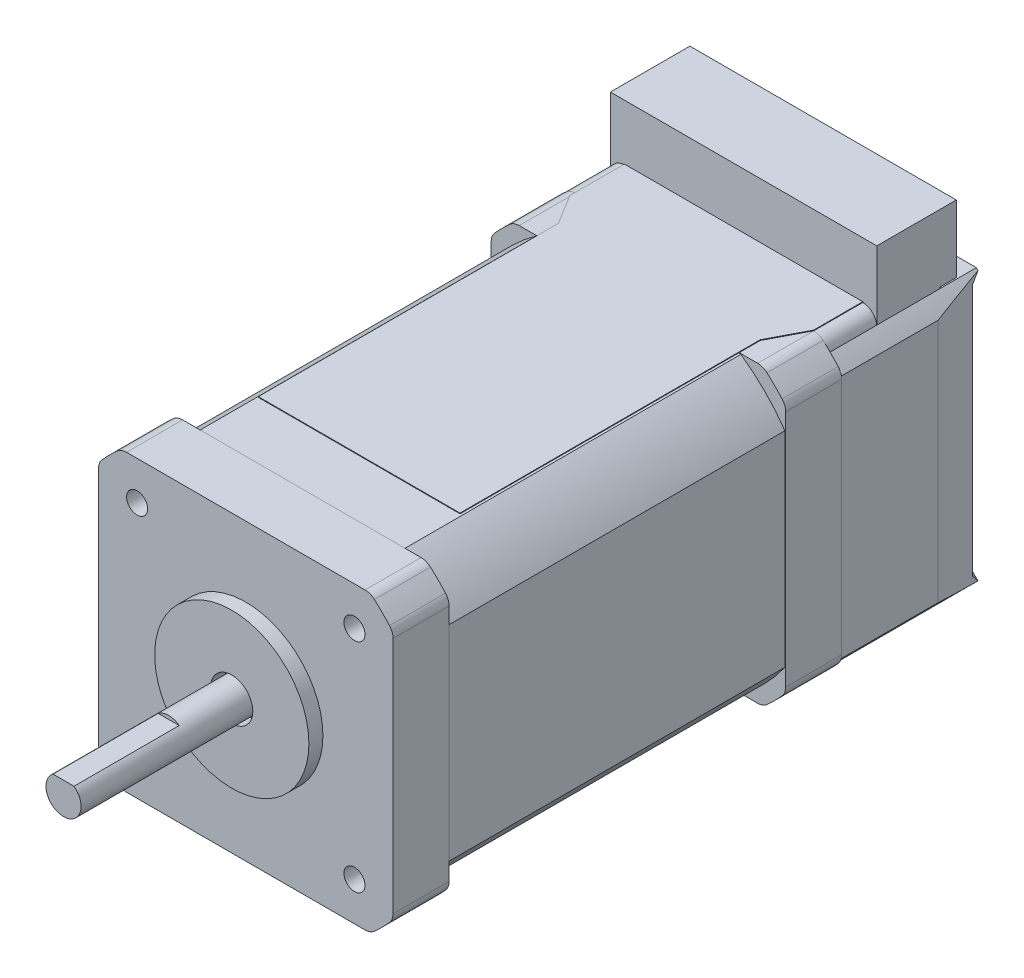
SolidWorks part; units mm, degrees
ref_plane "Ebene vorne" through (0, 0, 0) normal (0, 0, 1) x (1, 0, 0)
ref_plane "Ebene oben" through (0, 0, 0) normal (0, 1, 0) x (1, 0, 0)
ref_plane "Ebene rechts" through (0, 0, 0) normal (1, 0, 0) x (0, 0, -1)
sketch "Skizze1" plane through (0, 0, 0) normal (0, 0, 1) x (1, 0, 0)
  line L1 (-21, -21) -> (21, -21)
  line L2 (-21, -21) -> (-21, 21)
  line L3 (-21, 21) -> (21, 21)
  line L4 (21, -21) -> (21, 21)
  line L5 (-21, -21) -> (21, 21) construction
  line L6 (-21, 21) -> (21, -21) construction
  point P0 (0, 0)
  dimension "D1" = 42
  dimension "D2" = 42
extrude "Aufsatz-Linear austragen1" add sketch "Skizze1" along normal mid plane 64
sketch "Skizze2" plane through (0, 0, 32) normal (0, 0, 1) x (1, 0, 0)
  circle A0 centre (0, 0) radius 27.5
  dimension "D1" = 55
sketch "Skizze3" plane through (0, 0, 32) normal (0, 0, 1) x (1, 0, 0)
  circle A0 centre (0, 0) radius 11
  circle A1 centre (0, 0) radius 3
  dimension "D1" = 22
  dimension "D2" = 6
extrude "Aufsatz-Linear austragen2" add sketch "Skizze3" along normal blind 2
sketch "Skizze4" plane through (0, 0, 32) normal (0, 0, 1) x (1, 0, 0)
  line L1 (-15.5, -15.5) -> (15.5, -15.5)
  line L2 (-15.5, -15.5) -> (-15.5, 15.5)
  line L3 (-15.5, 15.5) -> (15.5, 15.5)
  line L4 (15.5, -15.5) -> (15.5, 15.5)
  line L5 (-15.5, -15.5) -> (15.5, 15.5) construction
  line L6 (-15.5, 15.5) -> (15.5, -15.5) construction
  point P0 (0, 0)
  dimension "D1" = 31
  dimension "D2" = 31
sketch "Skizze5" plane through (0, 0, 32) normal (0, 0, 1) x (1, 0, 0)
  circle A0 centre (-15.5, 15.5) radius 1.5
  circle A1 centre (15.5, 15.5) radius 1.5
  circle A2 centre (-15.5, -15.5) radius 1.5
  circle A3 centre (15.5, -15.5) radius 1.5
  dimension "D1" = 3
extrude "Schnitt-Linear austragen2" cut sketch "Skizze5" against normal blind 10
sketch "Skizze6" plane through (0, 0, 34) normal (0, 0, 1) x (1, 0, 0)
  circle A0 centre (0, 0) radius 2.5
  dimension "D1" = 5
extrude "Aufsatz-Linear austragen3" add sketch "Skizze6" along normal blind 24 and the other way blind 10
sketch "Skizze10" plane through (0, 0, 58) normal (0, 0, 1) x (1, 0, 0)
  line L1 (-6.775, 11.5682) -> (7.5774, 11.5682)
  line L2 (-6.775, 11.5682) -> (-6.775, 2)
  line L3 (-6.775, 2) -> (7.5774, 2)
  line L4 (7.5774, 11.5682) -> (7.5774, 2)
  dimension "D1" = 2
extrude "Schnitt-Linear austragen4" cut sketch "Skizze10" against normal blind 15
ref_plane "Ebene1" through (0, 0, 0) normal (1, 0, 0) x (0, 0, -1)
ref_plane "Ebene2" through (0, 0, 0) normal (0, 1, 0) x (1, 0, 0)
extrude "Schnitt-Linear austragen5" cut sketch "Skizze2" against normal through all flip side to cut
sketch "Skizze11" plane through (0, 0, 32) normal (0, 0, 1) x (1, 0, 0)
  line L0 (-14.6096, 20.9) -> (14.6096, 20.9)
  line L1 (-20.9, 14.6096) -> (-20.9, -14.6096)
  line L2 (-14.6096, -20.9) -> (14.6096, -20.9)
  line L3 (20.9, -14.6096) -> (20.9, 14.6096)
  line L4 (21, -17.7553) -> (21, 17.7553) construction
  line L5 (17.7553, 21) -> (-17.7553, 21) construction
  line L6 (-21, 17.7553) -> (-21, -17.7553) construction
  line L7 (-17.7553, -21) -> (17.7553, -21) construction
  arc A0 (-20.9, -14.6096) -> (-14.6096, -20.9) centre (0, 0) ccw
  circle A1 centre (0, 0) radius 28.2253
  arc A2 (14.6096, -20.9) -> (20.9, -14.6096) centre (0, 0) ccw
  arc A3 (20.9, 14.6096) -> (14.6096, 20.9) centre (0, 0) ccw
  arc A4 (-14.6096, 20.9) -> (-20.9, 14.6096) centre (0, 0) ccw
  dimension "D1" = 51
  dimension "D2" = 0.1
  dimension "D3" = 0.1
  dimension "D4" = 0.1
  dimension "D5" = 0.1
extrude "Schnitt-Linear austragen6" cut sketch "Skizze11" against normal offset from surface (48 mm away) 8 from offset 8 up to face at (0, 0, -32) offset against normal yes
fillet "Verrundung1" radius 2 16 edges at (17.7553, -21, 28) (21, -17.7553, 28) (21, -17.7553, -28) (17.7553, -21, -28) (-21, -17.7553, -28) (-17.7553, -21, -28) (-17.7553, -21, 28) (-21, -17.7553, 28) (-17.7553, 21, 28) (-21, 17.7553, 28) (-21, 17.7553, -28) (-17.7553, 21, -28) (21, 17.7553, -28) (17.7553, 21, -28) (21, 17.7553, 28) (17.7553, 21, 28)
sketch "Skizze12" plane through (0, 0, -32) normal (0, 0, -1) x (-1, 0, 0)
  line L0 (-17.0074, 21) -> (17.0074, 21) construction
  line L1 (-19, 21) -> (19, 21)
  line L2 (-19, 21) -> (-19, 6)
  line L3 (-19, 6) -> (19, 6)
  line L4 (19, 21) -> (19, 6)
  dimension "D1" = 19
  dimension "D2" = 19
  dimension "D3" = 15
extrude "Aufsatz-Linear austragen4" add sketch "Skizze12" along normal blind 8 separate body
fillet "Verrundung2" radius 2 2 edges at (-19, 21, -36) (19, 21, -36)
sketch "Skizze13" plane through (0, 0, -40) normal (0, 0, -1) x (-1, 0, 0)
  line L1 (-19, 6) -> (19, 6)
  line L2 (-19, 6) -> (-19, 19)
  line L3 (-19, 19) -> (19, 19)
  line L4 (19, 6) -> (19, 19)
  arc A0 (19, 19) -> (17, 21) centre (17, 19) ccw construction
extrude "Aufsatz-Linear austragen5" add sketch "Skizze13" along normal blind 8 separate body
sketch "Skizze15" plane through (0, 19, 0) normal (0, 1, 0) x (1, 0, 0)
  line L0 (-19, 40) -> (19, 40) construction
  line L1 (0.5, 40.6) -> (3, 40.6)
  line L2 (0.5, 40.6) -> (0.5, 47.4)
  line L3 (0.5, 47.4) -> (3, 47.4)
  line L4 (3, 40.6) -> (3, 47.4)
  line L5 (-19, 48) -> (19, 48) construction
  dimension "D1" = 2.5
  dimension "D2" = 0.5
  dimension "D3" = 0.6
  dimension "D4" = 0.6
extrude "Schnitt-Linear austragen7" cut sketch "Skizze15" against normal blind 8
pattern_linear "Lineares Muster1" count 5 spacing 3.5 along (1, 0, 0) of "Schnitt-Linear austragen7"
mirror "Spiegeln1" about plane through (0, 0, 0) normal (1, 0, 0) of "Lineares Muster1", "Schnitt-Linear austragen7"
sketch "Skizze16" plane through (0, 0, -32) normal (0, 0, -1) x (-1, 0, 0)
  line L0 (-19.2, 19.4075) -> (-19.2, 5.7074)
  line L1 (-19.2, 5.7074) -> (19.2, 5.7074)
  line L2 (19.2, 5.7074) -> (19.2, 19.4075)
  line L3 (-21, 17.4439) -> (-21, -17.4439)
  line L4 (-17.4439, -21) -> (17.4439, -21)
  line L5 (21, -17.4439) -> (21, 17.4439)
  arc A0 (-19.2, 19.4075) -> (-21, 17.4439) centre (0, 0) ccw
  arc A1 (21, 17.4439) -> (19.2, 19.4075) centre (0, 0) ccw
  arc A2 (-21, -17.4439) -> (-17.4439, -21) centre (0, 0) ccw
  arc A3 (17.4439, -21) -> (21, -17.4439) centre (0, 0) ccw
  dimension "D1" = 19.2
  dimension "D3" = 54.6
  dimension "D2" = 19.2
  dimension "D4" = 21
  dimension "D5" = 21
  dimension "D6" = 21
extrude "Aufsatz-Linear austragen6" add sketch "Skizze16" along normal blind 16 separate body
sketch "Skizze17" plane through (0, 0, -48) normal (0, 0, -1) x (-1, 0, 0)
  line L0 (-19.2, 19.4075) -> (19.2, 19.4075)
  line L1 (21, 17.4439) -> (21, -17.4439)
  line L2 (-21, -17.4439) -> (-21, 17.4439)
  line L3 (-17.4439, -21) -> (17.4439, -21)
  arc A0 (17.4439, -21) -> (21, -17.4439) centre (0, 0) ccw
  arc A1 (21, 17.4439) -> (19.2, 19.4075) centre (0, 0) ccw
  arc A2 (-21, -17.4439) -> (-17.4439, -21) centre (0, 0) ccw
  arc A3 (-19.2, 19.4075) -> (-21, 17.4439) centre (0, 0) ccw
extrude "Aufsatz-Linear austragen7" add sketch "Skizze17" along normal blind 5
sketch "Skizze18" plane through (0, 0, -53) normal (0, 0, -1) x (-1, 0, 0)
  line L0 (0, 2.3344) -> (0, -9.554) construction
  line L1 (0, 22.3327) -> (0, -22.3327) construction
  line L2 (5.2211, 2.3344) -> (5.2211, -9.554)
  line L3 (-5.2211, 2.3344) -> (-5.2211, -9.554)
  line L4 (-9.6893, 19.4075) -> (-2.5, 12.2182)
  line L5 (19.2, 19.4075) -> (-19.2, 19.4075) construction
  line L6 (-2.5, 12.2182) -> (-2.5, 6.9181)
  line L7 (-2.5, -14.9333) -> (-8.5667, -21)
  line L8 (-17.4439, -21) -> (17.4439, -21) construction
  line L9 (2.5, 12.2182) -> (9.6893, 19.4075)
  line L10 (9.6893, 19.4075) -> (-9.6893, 19.4075)
  line L11 (2.5, 12.2182) -> (2.5, 6.9181)
  line L12 (2.5, -14.9333) -> (8.5667, -21)
  line L13 (8.5667, -21) -> (-8.5667, -21)
  line L14 (-2.5, -14.1377) -> (-2.5, -14.9333)
  line L15 (2.5, -14.1377) -> (2.5, -14.9333)
  arc A0 (5.2211, 2.3344) -> (2.5, 6.9181) centre (0, 2.3344) ccw
  arc A1 (-5.2211, -9.554) -> (-2.5, -14.1377) centre (0, -9.554) ccw
  arc A2 (-2.5, 6.9181) -> (-5.2211, 2.3344) centre (0, 2.3344) ccw
  arc A3 (2.5, -14.1377) -> (5.2211, -9.554) centre (0, -9.554) ccw
  point P5 (0, -3.6098)
  dimension "D1" = 2.5
  dimension "D2" = 2.5
  dimension "D3" = 45
  dimension "D4" = 45
extrude "Schnitt-Linear austragen8" cut sketch "Skizze18" against normal blind 1
sketch "Skizze19" plane through (0, 0, -52) normal (0, 0, -1) x (-1, 0, 0)
  line L0 (0, 7.979) -> (0, 11.017) construction
  line L1 (0, 22.3327) -> (0, -22.3327) construction
  line L2 (-0.7738, 7.979) -> (-0.7738, 11.017)
  line L3 (0.7738, 7.979) -> (0.7738, 11.017)
  arc A0 (-0.7738, 7.979) -> (0.7738, 7.979) centre (0, 7.979) ccw
  arc A1 (0.7738, 11.017) -> (-0.7738, 11.017) centre (0, 11.017) ccw
  point P5 (0, 9.498)
extrude "Aufsatz-Linear austragen8" add sketch "Skizze19" along normal blind 1
sketch "Skizze20" plane through (0, 0, -53) normal (0, 0, -1) x (-1, 0, 0)
  line L1 (-11.6444, 10.6744) -> (-11.6444, -9.9681)
  line L4 (-24.1419, -18.4477) -> (-24.1419, 18.4477)
  line L6 (-20.124, 18.4477) -> (-11.6444, 10.6744)
  line L7 (-20.124, 18.4477) -> (-24.1419, 18.4477)
  line L8 (-20.124, 18.4477) -> (-20.124, -18.4477) construction
  line L9 (-20.124, -18.4477) -> (-11.6444, -9.9681)
  line L10 (-20.124, -18.4477) -> (-24.1419, -18.4477)
  arc A0 (-21, -17.4439) -> (-17.4439, -21) centre (0, 0) ccw construction
  arc A1 (-19.2, 19.4075) -> (-21, 17.4439) centre (0, 0) ccw construction
extrude "Schnitt-Linear austragen9" cut sketch "Skizze20" against normal blind 1
mirror "Spiegeln2" about plane through (0, 0, 0) normal (1, 0, 0) of "Schnitt-Linear austragen9"
chamfer "Fase1" distance 1 angle 45 18 edges at (-15.8842, 14.561, -53) (-11.6444, 0.3532, -53) (-15.8842, -14.2079, -53) (6.0947, 15.8128, -53) (2.5, 9.5681, -53) (4.4896, 4.9996, -53) (5.2211, -3.6098, -53) (4.4896, -12.2192, -53) (5.5334, -17.9666, -53) (-5.5334, -17.9666, -53) (-4.4896, -12.2192, -53) (-5.2211, -3.6098, -53) (-4.4896, 4.9996, -53) (-2.5, 9.5681, -53) (-6.0947, 15.8128, -53) (15.8842, -14.2079, -53) (11.6444, 0.3532, -53) (15.8842, 14.561, -53)
sketch "Skizze21" plane through (0, 19.4075, 0) normal (0, 1, 0) x (1, 0, 0)
  line L0 (19.4347, 53) -> (21.4638, 43.6127)
  line L1 (21.4638, 43.6127) -> (21.4638, 53)
  line L2 (21.4638, 53) -> (19.4347, 53)
  line L3 (-19.4347, 53) -> (-21.351, 43.7732)
  line L4 (-21.351, 43.7732) -> (-21.351, 53)
  line L5 (-21.351, 53) -> (-19.4347, 53)
extrude "Schnitt-Linear austragen10" cut sketch "Skizze21" against normal through all
sketch "Skizze22" plane through (0, 0, -53) normal (0, 0, -1) x (-1, 0, 0)
  circle A0 centre (-15.8184, 4.5763) radius 3
  circle A1 centre (16.1585, -12.0298) radius 3
  dimension "D1" = 6
  dimension "D2" = 6
extrude "Schnitt-Linear austragen11" cut sketch "Skizze22" against normal blind 2
sketch "Skizze23" plane through (0, 21, 0) normal (0, 1, 0) x (1, 0, 0)
  line L0 (-17, 40) -> (-17.0074, 31.2165)
  line L1 (-17.0074, 32) -> (-17.0074, 24) construction
  line L2 (-17.0074, 31.2165) -> (-14.3864, 26.9892)
  line L3 (-17, 40) -> (17, 40)
  line L5 (17, 40) -> (17, 32)
  line L6 (17, 32) -> (14.3798, 26.9892)
  line L7 (14.3798, 26.9892) -> (14.3798, -15.8245)
  line L8 (14.3798, -15.8245) -> (-14.3864, -15.8245)
  line L9 (-14.3864, 26.9892) -> (-14.3864, -15.8245)
extrude "Aufsatz-Linear austragen9" add sketch "Skizze23" along normal blind 0.1
sketch "Skizze24" plane through (0, 19, 0) normal (0, 1, 0) x (1, 0, 0)
  line L0 (11.1035, 53) -> (19.2, 53) construction
  line L1 (-19, 39) -> (19, 39)
  line L2 (-19, 39) -> (-19, 50.3407)
  line L3 (-19, 50.3407) -> (19, 50.3407)
  line L4 (19, 39) -> (19, 50.3407)
  dimension "D1" = 19
  dimension "D2" = 19
  dimension "D3" = 14
  dimension "D4" = 2.6593
extrude "Aufsatz-Linear austragen10" add sketch "Skizze24" along normal blind 10 separate body
